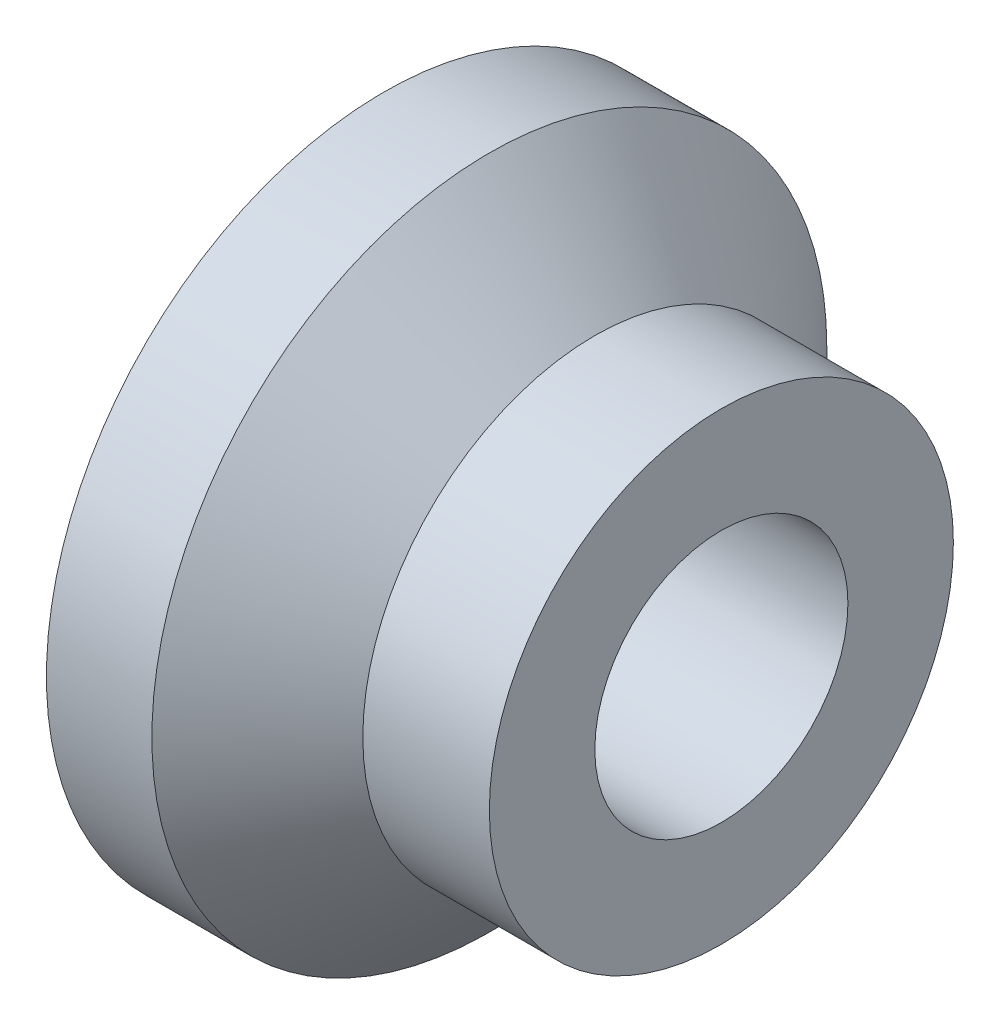
SolidWorks part; units mm, degrees
material "PVC 0.007 Plasticized"
ref_plane "Front Plane" through (0, 0, 0) normal (0, 0, 1) x (1, 0, 0)
ref_plane "Top Plane" through (0, 0, 0) normal (0, 1, 0) x (1, 0, 0)
ref_plane "Right Plane" through (0, 0, 0) normal (1, 0, 0) x (0, 0, -1)
sketch "Sketch1" plane through (0, 0, 0) normal (1, 0, 0) x (0, 0, -1)
  circle A0 centre (0, 0) radius 4
  circle A1 centre (0, 0) radius 1.5
  dimension "D1" = 8
  dimension "D2" = 3
extrude "Boss-Extrude1" add sketch "Sketch1" along normal blind 4
sketch "Sketch2" plane through (4, 0, 0) normal (1, 0, 0) x (0, 0, -1)
  circle A0 centre (0, 0) radius 2.75
  dimension "D1" = 5.5
extrude "Cut-Extrude1" cut sketch "Sketch2" against normal blind 1.5 flip side to cut
chamfer "Chamfer1" distance 1.25 angle 45 1 edges at (2.5, 0, -4)
